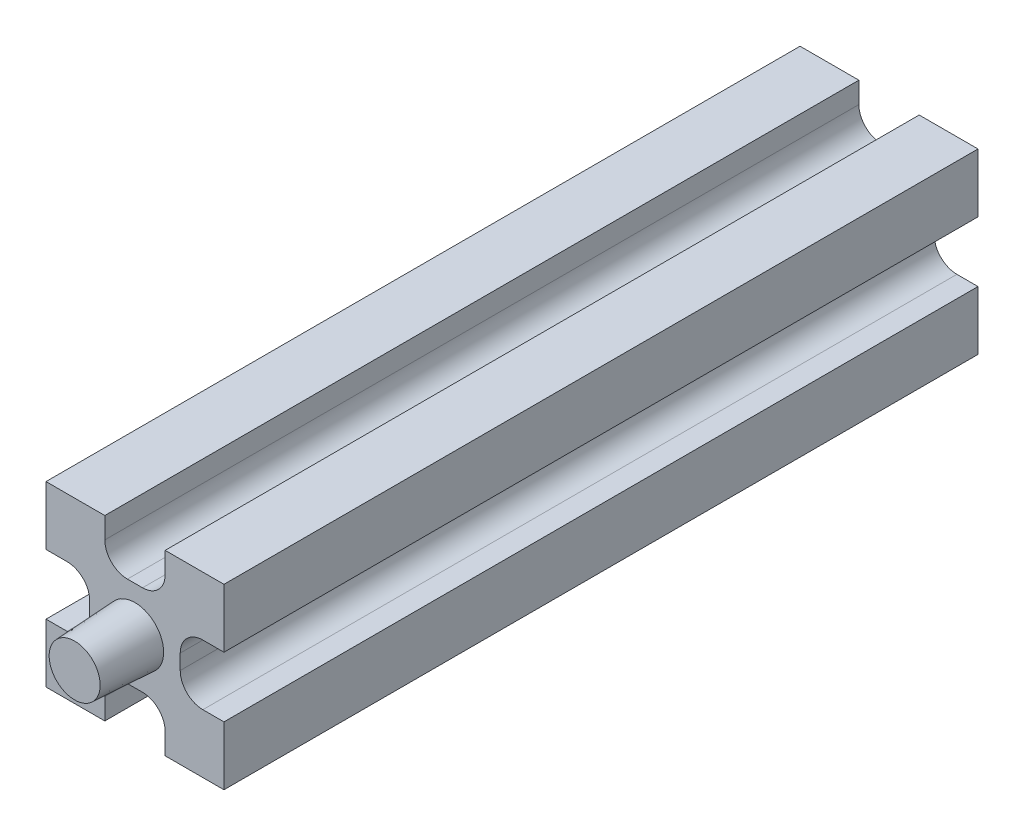
SolidWorks part; units mm, degrees
ref_plane "Alzado" through (0, 0, 0) normal (0, 0, 1) x (1, 0, 0)
ref_plane "Planta" through (0, 0, 0) normal (0, 1, 0) x (1, 0, 0)
ref_plane "Vista lateral" through (0, 0, 0) normal (1, 0, 0) x (0, 0, -1)
sketch "Croquis1" plane through (0, 0, 0) normal (0, 0, 1) x (1, 0, 0)
  line L0 (117743.4169, 152337.8366) -> (131743.4169, 152337.8366)
  line L1 (131743.4169, 152337.8366) -> (131743.4169, 161337.8366)
  line L2 (131743.4169, 161337.8366) -> (140743.4169, 161337.8366)
  line L3 (140743.4169, 161337.8366) -> (140743.4169, 175337.8366)
  line L4 (140743.4169, 175337.8366) -> (117743.4169, 175337.8366)
  line L5 (117743.4169, 175337.8366) -> (117743.4169, 152337.8366)
  line L6 (118743.4169, 152337.8366) -> (118743.4169, 166437.8366)
  line L7 (118743.4169, 174337.8366) -> (122843.4169, 174337.8366)
  line L8 (130743.4169, 152337.8366) -> (130743.4169, 162337.8366)
  line L9 (140743.4169, 162337.8366) -> (130743.4169, 162337.8366)
  line L10 (131743.4169, 161337.8366) -> (108743.4169, 161337.8366)
  line L11 (108743.4169, 161337.8366) -> (108743.4169, 162337.8366)
  line L12 (108743.4169, 162337.8366) -> (122843.4169, 162337.8366)
  line L13 (131743.4169, 161337.8366) -> (131743.4169, 184337.8366)
  line L14 (131743.4169, 184337.8366) -> (130743.4169, 184337.8366)
  line L15 (130743.4169, 184337.8366) -> (130743.4169, 170237.8366)
  line L16 (118743.4169, 174337.8366) -> (118743.4169, 184337.8366)
  line L17 (118743.4169, 184337.8366) -> (117743.4169, 184337.8366)
  line L18 (117743.4169, 184337.8366) -> (117743.4169, 175337.8366)
  line L19 (118743.4169, 174337.8366) -> (108743.4169, 174337.8366)
  line L20 (108743.4169, 174337.8366) -> (108743.4169, 175337.8366)
  line L21 (108743.4169, 175337.8366) -> (117743.4169, 175337.8366)
  line L22 (108743.4169, 174337.8366) -> (108743.4169, 162337.8366)
  line L23 (118743.4169, 184337.8366) -> (130743.4169, 184337.8366)
  line L24 (122743.4169, 174237.8366) -> (122743.4169, 172837.8366)
  line L25 (124243.4169, 171337.8366) -> (125243.4169, 171337.8366)
  line L26 (126743.4169, 172837.8366) -> (126743.4169, 174237.8366)
  line L27 (118843.4169, 170337.8366) -> (120243.4169, 170337.8366)
  line L28 (121743.4169, 168837.8366) -> (121743.4169, 167837.8366)
  line L29 (120243.4169, 166337.8366) -> (118843.4169, 166337.8366)
  line L30 (130643.4169, 170337.8366) -> (129243.4169, 170337.8366)
  line L31 (127743.4169, 168837.8366) -> (127743.4169, 167837.8366)
  line L32 (129243.4169, 166337.8366) -> (130643.4169, 166337.8366)
  line L33 (122743.4169, 162437.8366) -> (122743.4169, 163837.8366)
  line L34 (124243.4169, 165337.8366) -> (125243.4169, 165337.8366)
  line L35 (126743.4169, 163837.8366) -> (126743.4169, 162337.8366)
  line L36 (121743.4169, 168337.8366) -> (127743.4169, 168337.8366) construction
  line L37 (118743.4169, 170237.8366) -> (120243.4169, 170237.8366)
  line L38 (118843.4169, 174237.8366) -> (122743.4169, 174237.8366)
  line L39 (121643.4169, 168837.8366) -> (121643.4169, 167837.8366)
  line L40 (118843.4169, 162437.8366) -> (118843.4169, 166337.8366)
  line L41 (118843.4169, 162437.8366) -> (122743.4169, 162437.8366)
  line L42 (130643.4169, 174237.8366) -> (130643.4169, 170337.8366)
  line L43 (120243.4169, 166437.8366) -> (118743.4169, 166437.8366)
  line L44 (118743.4169, 174237.8366) -> (140743.4169, 174237.8366) construction
  line L45 (122843.4169, 162337.8366) -> (122843.4169, 163837.8366)
  line L46 (124243.4169, 165237.8366) -> (125243.4169, 165237.8366)
  line L47 (126643.4169, 163837.8366) -> (126643.4169, 162337.8366)
  line L48 (130743.4169, 170237.8366) -> (129243.4169, 170237.8366)
  line L49 (127843.4169, 168837.8366) -> (127843.4169, 167837.8366)
  line L50 (129243.4169, 166437.8366) -> (130743.4169, 166437.8366)
  line L51 (122843.4169, 174337.8366) -> (122843.4169, 172837.8366)
  line L52 (124243.4169, 171437.8366) -> (125243.4169, 171437.8366)
  line L53 (126643.4169, 172837.8366) -> (126643.4169, 174337.8366)
  line L54 (130643.4169, 166337.8366) -> (130643.4169, 162437.8366)
  line L55 (130743.4169, 166437.8366) -> (130743.4169, 162337.8366)
  line L56 (129243.4169, 166337.8366) -> (130743.4169, 166337.8366) construction
  line L57 (130743.4169, 170337.8366) -> (129243.4169, 170337.8366) construction
  line L58 (126643.4169, 174337.8366) -> (140743.4169, 174337.8366)
  line L59 (118743.4169, 174337.8366) -> (140743.4169, 174337.8366) construction
  line L60 (126743.4169, 174237.8366) -> (130643.4169, 174237.8366)
  line L61 (126743.4169, 172837.8366) -> (126743.4169, 174337.8366) construction
  line L62 (122743.4169, 174337.8366) -> (122743.4169, 172837.8366) construction
  line L63 (118743.4169, 170237.8366) -> (118743.4169, 174337.8366)
  line L64 (118843.4169, 170337.8366) -> (118843.4169, 174237.8366)
  line L65 (118743.4169, 170337.8366) -> (120243.4169, 170337.8366) construction
  line L66 (120243.4169, 166337.8366) -> (118743.4169, 166337.8366) construction
  line L67 (126743.4169, 162437.8366) -> (130643.4169, 162437.8366)
  line L68 (122743.4169, 162337.8366) -> (122743.4169, 163837.8366) construction
  line L69 (126643.4169, 162337.8366) -> (130743.4169, 162337.8366)
  arc A0 (125243.4169, 165337.8366) -> (126743.4169, 163837.8366) centre (125243.4169, 163837.8366) cw
  arc A1 (122743.4169, 163837.8366) -> (124243.4169, 165337.8366) centre (124243.4169, 163837.8366) cw
  arc A2 (127743.4169, 167837.8366) -> (129243.4169, 166337.8366) centre (129243.4169, 167837.8366) ccw
  arc A3 (129243.4169, 170337.8366) -> (127743.4169, 168837.8366) centre (129243.4169, 168837.8366) ccw
  arc A4 (125243.4169, 171337.8366) -> (126743.4169, 172837.8366) centre (125243.4169, 172837.8366) ccw
  arc A5 (122743.4169, 172837.8366) -> (124243.4169, 171337.8366) centre (124243.4169, 172837.8366) ccw
  arc A6 (120243.4169, 170337.8366) -> (121743.4169, 168837.8366) centre (120243.4169, 168837.8366) cw
  arc A7 (121743.4169, 167837.8366) -> (120243.4169, 166337.8366) centre (120243.4169, 167837.8366) cw
  circle A8 centre (124743.4169, 168337.8366) radius 2000
  arc A9 (120243.4169, 170237.8366) -> (121643.4169, 168837.8366) centre (120243.4169, 168837.8366) cw
  arc A10 (121643.4169, 167837.8366) -> (120243.4169, 166437.8366) centre (120243.4169, 167837.8366) cw
  arc A11 (122843.4169, 163837.8366) -> (124243.4169, 165237.8366) centre (124243.4169, 163837.8366) cw
  arc A12 (125243.4169, 165237.8366) -> (126643.4169, 163837.8366) centre (125243.4169, 163837.8366) cw
  arc A13 (129243.4169, 170237.8366) -> (127843.4169, 168837.8366) centre (129243.4169, 168837.8366) ccw
  arc A14 (127843.4169, 167837.8366) -> (129243.4169, 166437.8366) centre (129243.4169, 167837.8366) ccw
  arc A15 (122843.4169, 172837.8366) -> (124243.4169, 171437.8366) centre (124243.4169, 172837.8366) ccw
  arc A16 (125243.4169, 171437.8366) -> (126643.4169, 172837.8366) centre (125243.4169, 172837.8366) ccw
  circle A17 centre (124743.4169, 168337.8366) radius 1900
  point P34 (126743.4169, 163087.8366)
  point P39 (126743.4169, 165337.8366)
  point P42 (122743.4169, 165337.8366)
  point P45 (127743.4169, 166337.8366)
  point P48 (127743.4169, 170337.8366)
  point P51 (126743.4169, 171337.8366)
  point P54 (122743.4169, 171337.8366)
  point P57 (121743.4169, 170337.8366)
  point P60 (121743.4169, 166337.8366)
  dimension "D21" = 1500
  dimension "D22" = 4000
  dimension "D1" = 12000
  dimension "D2" = 1000
  dimension "D3" = 1000
  dimension "D4" = 1000
  dimension "D5" = 1000
  dimension "D6" = 12000
  dimension "D7" = 9000
  dimension "D8" = 9000
  dimension "D9" = 9000
  dimension "D10" = 9000
  dimension "D11" = 4000
  dimension "D12" = 4000
  dimension "D13" = 4000
  dimension "D14" = 4000
  dimension "D18" = 4000
  dimension "D19" = 4000
  dimension "D20" = 3000
  dimension "D23" = 100
  dimension "D24" = 100
  dimension "D25" = 100
  dimension "D26" = 100
ref_plane "Plano1" through (0, 161337.8366, 0) normal (0, 1, 0) x (1, 0, 0)
ref_plane "Plano2" through (0, 175337.8366, 0) normal (0, 1, 0) x (1, 0, 0)
ref_plane "Plano3" through (117743.4169, 0, 0) normal (1, 0, 0) x (0, 0, -1)
ref_plane "Plano4" through (131743.4169, 0, 0) normal (1, 0, 0) x (0, 0, -1)
ref_plane "Plano5" through (113243.4169, 0, 0) normal (1, 0, 0) x (0, 0, -1)
ref_plane "Plano6" through (0, 179837.8366, 0) normal (0, 1, 0) x (1, 0, 0)
ref_plane "Plano7" through (136243.4169, 0, 0) normal (1, 0, 0) x (0, 0, -1)
ref_plane "Plano8" through (0, 156837.8366, 0) normal (0, 1, 0) x (1, 0, 0)
sketch "Croquis2" plane through (0, 156837.8366, 0) normal (0, 1, 0) x (1, 0, 0)
  line L0 (117743.4169, 0) -> (131743.4169, 0) construction
  line L1 (117743.4169, 0) -> (131743.4169, 0)
  line L2 (131743.4169, 0) -> (131743.4169, 8000)
  line L3 (131743.4169, 8000) -> (130743.4169, 8000)
  line L4 (130743.4169, 8000) -> (130743.4169, 1000)
  line L5 (130743.4169, 1000) -> (118743.4169, 1000)
  line L6 (118743.4169, 1000) -> (118743.4169, 8000)
  line L7 (118743.4169, 8000) -> (117743.4169, 8000)
  line L8 (117743.4169, 8000) -> (117743.4169, 0)
  spline S0 degree 2 poles (130743.4169, 8000) (128761.6752, 7234.3483) (128743.4169, 1000) knots 0 0 0 0.590989 0.590989 0.590989
  spline S1 degree 2 poles (118743.4169, 8000) (120739.8111, 7120.5788) (120743.4169, 1000) knots 0 0 0 0.514461 0.514461 0.514461
  dimension "D1" = 1000
  dimension "D2" = 1000
  dimension "D3" = 1000
  dimension "D4" = 7000
  dimension "D5" = 7000
  dimension "D6" = 2000
  dimension "D7" = 2000
sketch "Croquis3" plane through (0, 179837.8366, 0) normal (0, 1, 0) x (1, 0, 0)
  line L0 (118743.4169, 1000) -> (118743.4169, 8000) construction
  line L1 (130743.4169, 1000) -> (118743.4169, 1000) construction
  line L2 (130743.4169, 8000) -> (130743.4169, 1000) construction
  line L3 (118743.4169, 1000) -> (118743.4169, 8000)
  line L4 (130743.4169, 1000) -> (118743.4169, 1000)
  line L5 (130743.4169, 8000) -> (130743.4169, 1000)
  parabola Q0 (118743.4169, 8000) -> (120743.4169, 1000) focus (118361.6774, 7241.9739) apex (118662.5082, 8033.1777) construction
  parabola Q1 (130743.4169, 8000) -> (128743.4169, 1000) focus (131040.6578, 7282.3326) apex (130778.3168, 8013.005) construction
  parabola Q2 (118743.4169, 8000) -> (120743.4169, 1000) focus (118361.6774, 7241.9739) apex (118662.5082, 8033.1777)
  parabola Q3 (130743.4169, 8000) -> (128743.4169, 1000) focus (131040.6578, 7282.3326) apex (130778.3168, 8013.005)
sketch "Croquis4" plane through (113243.4169, 0, 0) normal (1, 0, 0) x (0, 0, -1)
  line L0 (0, 174337.8366) -> (0, 162337.8366) construction
  line L1 (0, 174337.8366) -> (0, 162337.8366)
  line L2 (0, 162337.8366) -> (8000, 162337.8366)
  line L3 (0, 174337.8366) -> (8000, 174337.8366)
  spline S0 degree 2 poles (8000, 162337.8366) (6698.659, 164240.8241) (0, 164337.8366) knots 0 0 0 0.70753 0.70753 0.70753
  spline S1 degree 2 poles (8000, 174337.8366) (6599.8546, 172118.7435) (0, 172337.8366) knots 0 0 0 0.648378 0.648378 0.648378
  dimension "D1" = 8000
  dimension "D2" = 2000
  dimension "D3" = 2000
sketch "Croquis5" plane through (136243.4169, 0, 0) normal (1, 0, 0) x (0, 0, -1)
  line L0 (0, 162337.8366) -> (8000, 162337.8366) construction
  line L1 (0, 174337.8366) -> (0, 162337.8366) construction
  line L2 (0, 174337.8366) -> (8000, 174337.8366) construction
  line L3 (0, 162337.8366) -> (8000, 162337.8366)
  line L4 (0, 174337.8366) -> (0, 162337.8366)
  line L5 (0, 174337.8366) -> (8000, 174337.8366)
  parabola Q0 (8000, 162337.8366) -> (0, 164337.8366) focus (7402.6379, 161620.0634) apex (8222.0253, 161894.2353) construction
  parabola Q1 (8000, 174337.8366) -> (0, 172337.8366) focus (7073.338, 175098.4045) apex (8142.0414, 174597.2807) construction
  parabola Q2 (8000, 162337.8366) -> (0, 164337.8366) focus (7402.6379, 161620.0634) apex (8222.0253, 161894.2353)
  parabola Q3 (8000, 174337.8366) -> (0, 172337.8366) focus (7073.338, 175098.4045) apex (8142.0414, 174597.2807)
extrude "Saliente-Extruir1" add sketch "Croquis1" against normal blind 50000 contours L28 A7 L29 L40 L41 L33 A1 L34 A0 L35 L67 L54 L32 A2 L31 A3 L30 L42 L60 L26 A4 L25 A5 L24 L38 L64 L27 A6 A8 | A8 A17 | A17 region at (126910.2941, 163137.8366, 0) region at (122799.9854, 168337.8366, 0) region at (124743.4169, 168337.8366, 0)
extrude "Saliente-Extruir2" add sketch "Croquis1<9>" along normal blind 4000 draft 3 contours A17 region at (124743.4169, 168337.8366, 0)
sketch "Croquis1<9>" plane through (0, 0, 0) normal (0, 0, 1) x (1, 0, 0) same geometry as "Croquis1"
